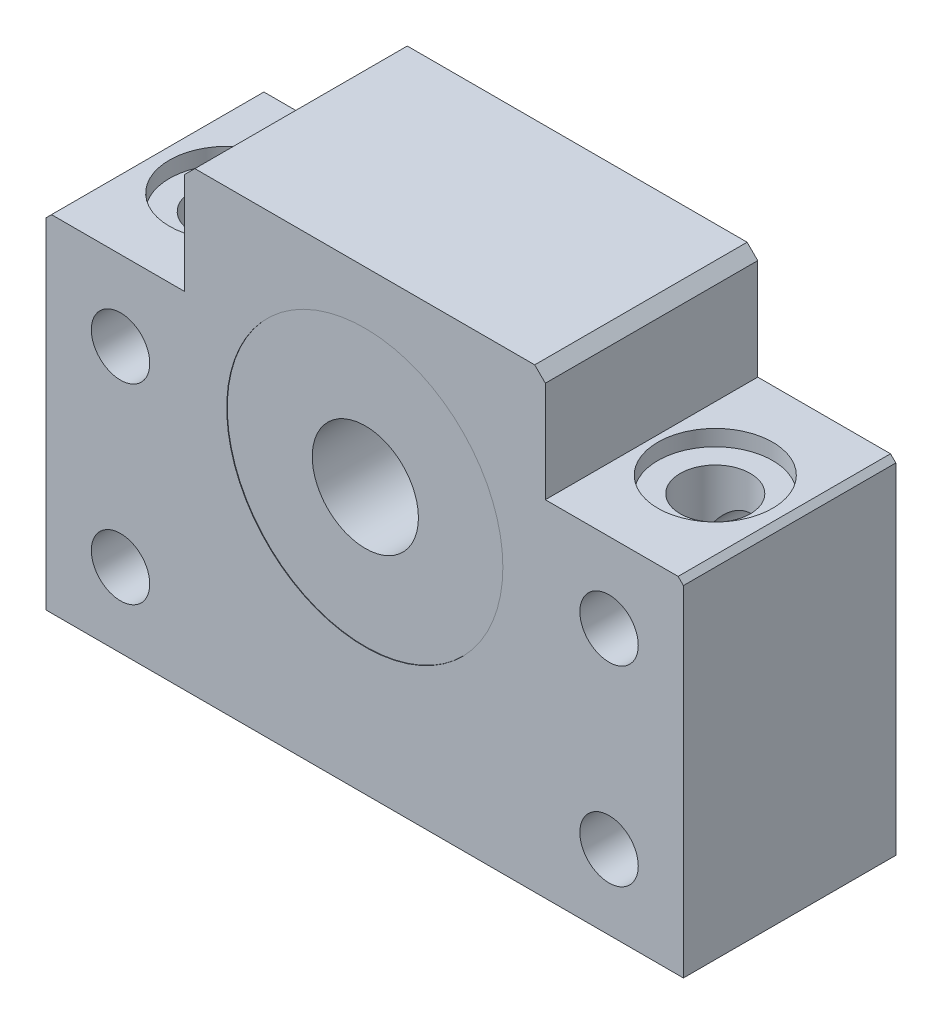
SolidWorks part; units mm, degrees
material "6061 Alloy"
ref_plane "Спереди" through (0, 0, 0) normal (0, 0, 1) x (1, 0, 0)
ref_plane "Сверху" through (0, 0, 0) normal (0, 1, 0) x (1, 0, 0)
ref_plane "Справа" through (0, 0, 0) normal (1, 0, 0) x (0, 0, -1)
sketch "Эскиз1" plane through (0, 0, 0) normal (0, 0, 1) x (1, 0, 0)
  line L0 (-30, -25) -> (-30, 7)
  line L1 (0, -25) -> (0, 18) construction
  line L2 (-30, -25) -> (30, -25)
  line L3 (-29.5, 7.5) -> (-17, 7.5)
  line L4 (17, 17) -> (17, 7.5)
  line L5 (-27.8123, 0) -> (-18.3765, 0) construction
  line L6 (-23, -25) -> (-23, 7.5) construction
  line L7 (-18.3765, -18) -> (-27.8123, -18) construction
  line L8 (18.3765, -18) -> (27.8123, -18) construction
  line L9 (23, -25) -> (23, 7.5) construction
  line L10 (27.8123, 0) -> (18.3765, 0) construction
  line L11 (-16, 18) -> (-17, 17)
  line L12 (29.5, 7.5) -> (17, 7.5)
  line L13 (30, -25) -> (30, 7)
  line L14 (16, 18) -> (-16, 18)
  line L15 (-30, 7) -> (-29.5, 7.5)
  line L16 (-17, 17) -> (-17, 7.5)
  line L17 (16, 18) -> (17, 17)
  line L18 (30, 7) -> (29.5, 7.5)
  circle A0 centre (-23, 0) radius 2.75
  circle A1 centre (-23, -18) radius 2.75
  circle A2 centre (23, -18) radius 2.75
  circle A3 centre (23, 0) radius 2.75
  circle A4 centre (0, 0) radius 13
  point P1 (-30, 7.5)
  point P8 (17, 18)
  point P29 (30, 7.5)
  point P36 (-17, 18)
  dimension "D1" = 60
  dimension "D2" = 46
  dimension "D8" = 5.5
  dimension "D3" = 30
  dimension "D4" = 18
  dimension "D5" = 25
  dimension "D6" = 32.5
  dimension "D7" = 43
  dimension "D9" = 34
extrude "Бобышка-Вытянуть1" add sketch "Эскиз1" along normal blind 10 and the other way blind 10
sketch "Эскиз2" plane through (0, 0, 0) normal (0, 1, 0) x (1, 0, 0)
  line L0 (29.5, -10) -> (17, -10) construction
  line L1 (-23, 10) -> (-23, -10) construction
  line L2 (-30, 0) -> (30, 0) construction
  line L8 (23, 10) -> (23, -10) construction
  circle A0 centre (-23, 0) radius 3.3
  circle A1 centre (23, 0) radius 3.3
  dimension "D1" = 46
  dimension "D2" = 10
extrude "Вырез-Вытянуть1" cut sketch "Эскиз2" against normal through all from offset 7.5
sketch "Эскиз3" plane through (0, 0, 0) normal (0, 1, 0) x (1, 0, 0)
  circle A0 centre (-23, 0) radius 5.4
  circle A1 centre (23, 0) radius 5.4
extrude "Вырез-Вытянуть2" cut sketch "Эскиз3" against normal blind 1.5 from offset 7.5
sketch "Эскиз4" plane through (0, 0, 0) normal (0, 0, 1) x (1, 0, 0)
  circle A0 centre (0, 0) radius 13
  circle A1 centre (0, 0) radius 5
extrude "Бобышка-Вытянуть2" add sketch "Эскиз4" along normal blind 4 and the other way blind 4 from offset 5.95
